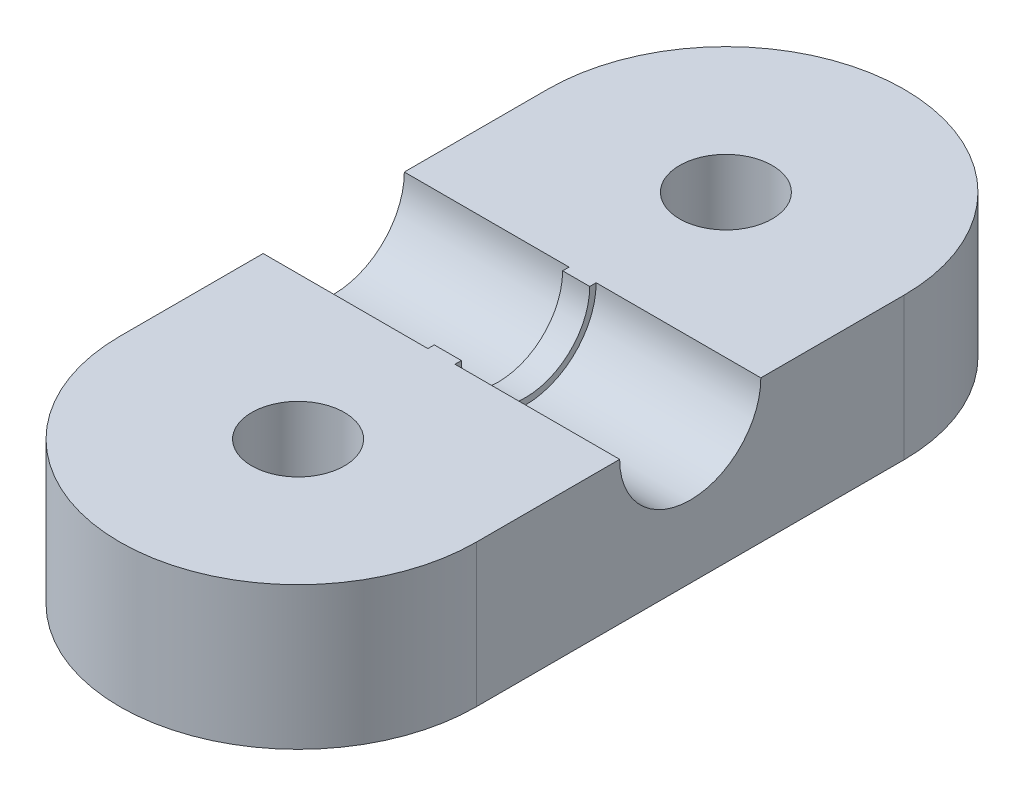
SolidWorks part; units mm, degrees
ref_plane "Front Plane" through (0, 0, 0) normal (0, 0, 1) x (1, 0, 0)
ref_plane "Top Plane" through (0, 0, 0) normal (0, 1, 0) x (1, 0, 0)
ref_plane "Right Plane" through (0, 0, 0) normal (1, 0, 0) x (0, 0, -1)
sketch "Sketch1" plane through (0, 0, 0) normal (0, 1, 0) x (1, 0, 0)
  line L0 (0, 27.5) -> (0, -27.5) construction
  line L1 (-12.5, 27.5) -> (12.5, 27.5)
  line L2 (-12.5, 27.5) -> (-12.5, -27.5)
  line L3 (-12.5, -27.5) -> (12.5, -27.5)
  line L4 (12.5, 27.5) -> (12.5, -27.5)
  line L5 (-12.5, 27.5) -> (12.5, -27.5) construction
  line L6 (-12.5, -27.5) -> (12.5, 27.5) construction
  line L7 (-12.5, 0) -> (12.5, 0) construction
  circle A0 centre (0, 15) radius 3.25
  circle A1 centre (0, -15) radius 3.25
  circle A2 centre (0, 15) radius 12.5
  circle A3 centre (0, -15) radius 12.5
  point P0 (0, 0)
  dimension "D3" = 6.5
  dimension "D1" = 25
  dimension "D4" = 30
extrude "Boss-Extrude1" add sketch "Sketch1" along normal blind 10 contours L2 A3 L4 A2 | A2 A0 | A3 A1 region at (8.5888, 0, -23.5888) region at (0, 0, 0) region at (0, 0, 2.8536)
sketch "Sketch2" plane through (12.5, 0, 0) normal (1, 0, 0) x (0, 0, -1)
  line L1 (15, 10) -> (-15, 10) construction
  circle A0 centre (0, 10) radius 4.95
  dimension "D1" = 9.9
extrude "Cut-Extrude1" cut sketch "Sketch2" against normal up to next
sketch "Sketch3" plane through (0, 0, 0) normal (1, 0, 0) x (0, 0, -1)
  line L0 (-4.95, 10) -> (4.95, 10)
  arc A0 (-4.95, 10) -> (4.95, 10) centre (0, 10) ccw construction
  arc A1 (-4.95, 10) -> (4.95, 10) centre (0, 10) ccw
  circle A2 centre (0, 10) radius 4.5
  dimension "D1" = 9
extrude "Boss-Extrude2" add sketch "Sketch3" along normal mid plane 1.9 contours A2 L0 A1 region at (0, 9.8893, -4.725)
